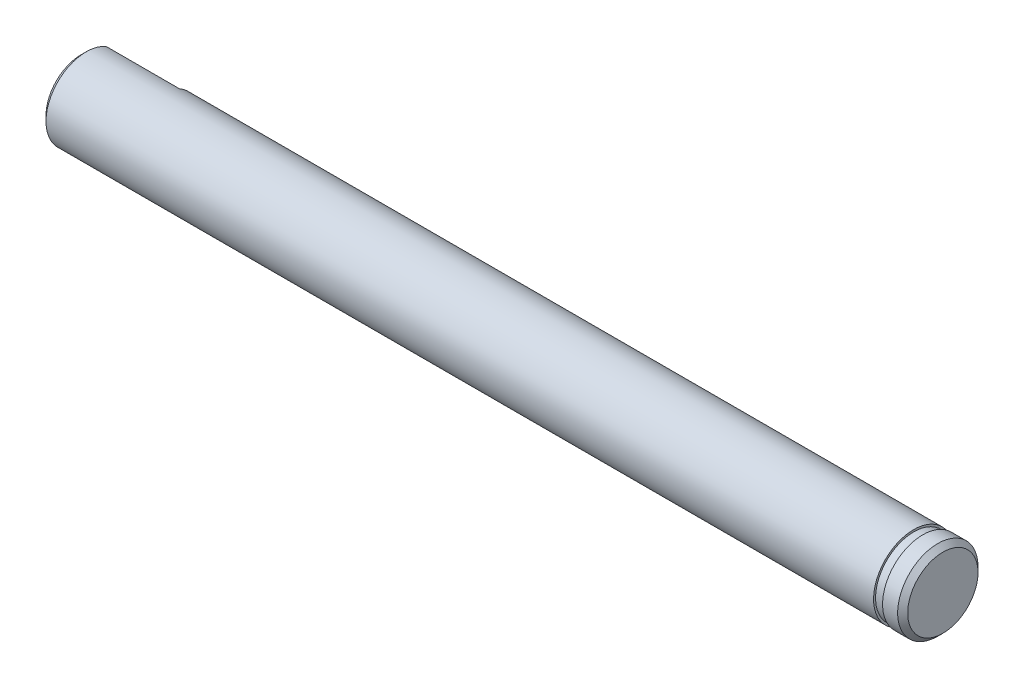
SolidWorks part; units mm, degrees
ref_plane "Front Plane" through (0, 0, 0) normal (0, 0, 1) x (1, 0, 0)
ref_plane "Top Plane" through (0, 0, 0) normal (0, 1, 0) x (1, 0, 0)
ref_plane "Right Plane" through (0, 0, 0) normal (1, 0, 0) x (0, 0, -1)
sketch "Sketch1" plane through (0, 0, 0) normal (1, 0, 0) x (0, 0, -1)
  line L0 (1.98, 3.4756) -> (1.98, -3.4756)
  line L1 (-4, -8) -> (1.98, -8) construction
  line L2 (-4, -8) -> (-4, 0) construction
  line L4 (1.98, -8) -> (1.98, 3.4756) construction
  arc A0 (1.98, 3.4756) -> (1.98, -3.4756) centre (0, 0) ccw
  dimension "D1" = 8
  dimension "D2" = 5.98
  dimension "D3" = 8
extrude "Boss-Extrude1" add sketch "Sketch1" along normal blind 7.8
sketch "Sketch2" plane through (7.8, 0, 0) normal (1, 0, 0) x (0, 0, -1)
  circle A0 centre (0, 0) radius 4
  dimension "8" = 8
extrude "Boss-Extrude2" add sketch "Sketch2" along normal blind 78
sketch "Sketch3" plane through (85.8, 0, 0) normal (1, 0, 0) x (0, 0, -1)
  circle A0 centre (0, 0) radius 3.8
  circle A1 centre (0, 0) radius 5
  dimension "D1" = 7.6
  dimension "D2" = 10
extrude "Cut-Extrude1" cut sketch "Sketch3" against normal blind 0.9 from offset 2 offset against normal yes
ref_plane "Plane1" through (0, 0, -4) normal (0, 0, -1) x (-1, 0, 0)
sketch "Sketch4" plane through (0, 0, -4) normal (0, 0, -1) x (-1, 0, 0)
  line L0 (0, 0) -> (-43.025, 0) construction
  circle A0 centre (-43.025, 0) radius 1.778
  point P4 (-43.025, 0)
  dimension "D2" = 3.556
  dimension "D1" = 43.025
extrude "Cut-Extrude2" cut sketch "Sketch4" against normal blind 1.905 draft 45
chamfer "Chamfer2" distance 0.5 angle 45 2 edges at (85.8, 0, -4) (0, 0, 4)
